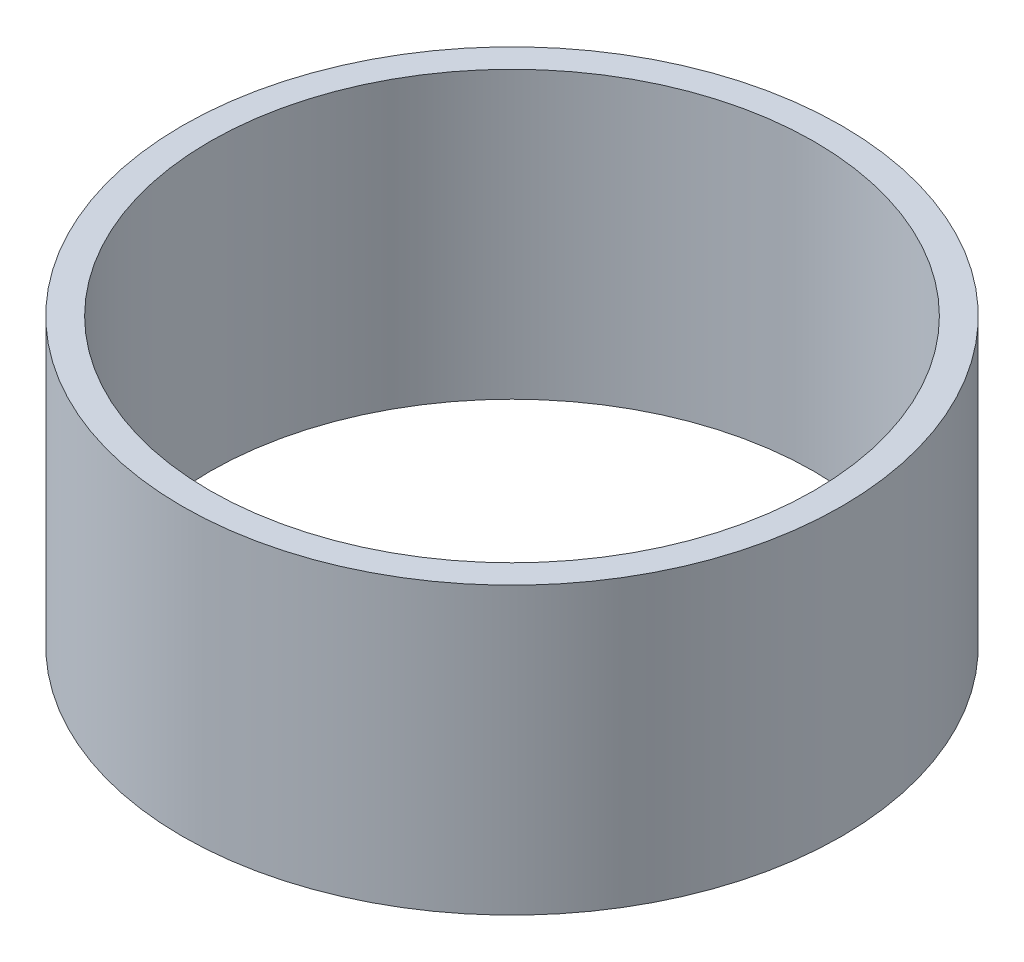
SolidWorks part; units mm, degrees
material "6061-T6 (SS)"
ref_plane "Front Plane" through (0, 0, 0) normal (0, 0, 1) x (1, 0, 0)
ref_plane "Top Plane" through (0, 0, 0) normal (0, 1, 0) x (1, 0, 0)
ref_plane "Right Plane" through (0, 0, 0) normal (1, 0, 0) x (0, 0, -1)
sketch "Sketch1" plane through (0, 0, 0) normal (0, 1, 0) x (1, 0, 0)
  circle A0 centre (0, 0) radius 76.2
  circle A1 centre (0, 0) radius 69.85
  dimension "D1" = 6.35
  dimension "D2" = 152.4
extrude "Boss-Extrude1" add sketch "Sketch1" along normal mid plane 66.04
